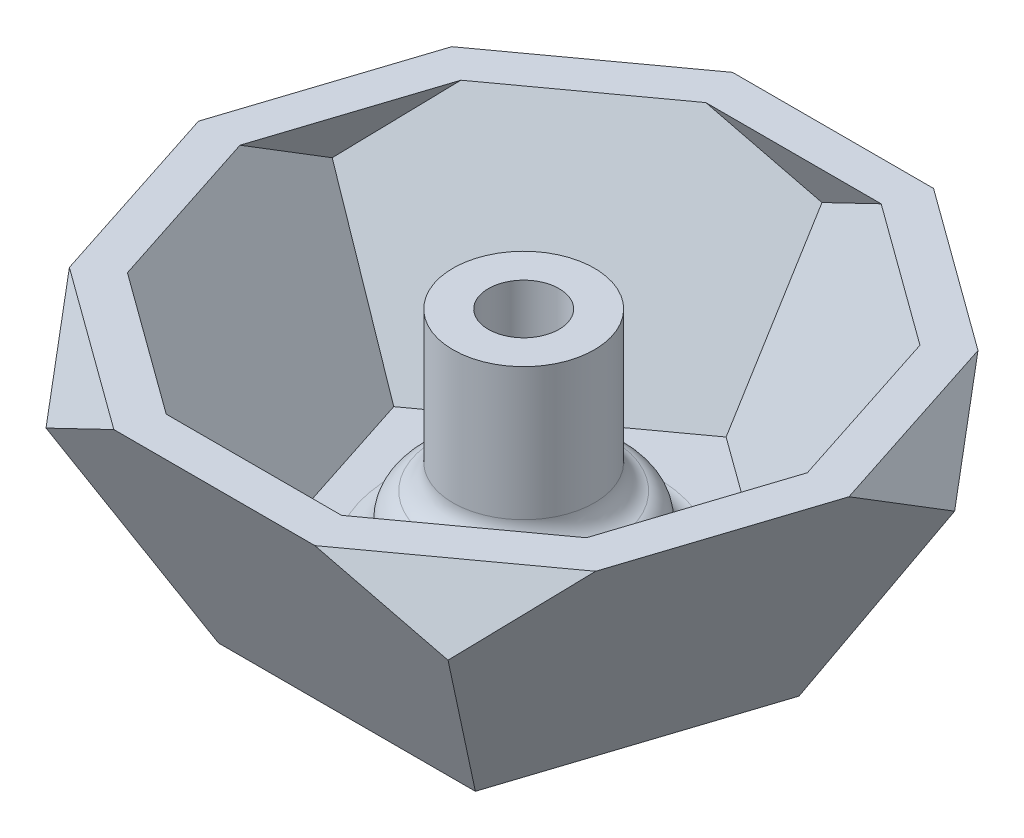
SolidWorks part; units mm, degrees
note: The reader was unsure of these and kept them because the rebuilt part matched: shared geometry of "Sketch10<3>".
ref_plane "Front Plane" through (0, 0, 0) normal (0, 0, 1) x (1, 0, 0)
ref_plane "Top Plane" through (0, 0, 0) normal (0, 1, 0) x (1, 0, 0)
ref_plane "Right Plane" through (0, 0, 0) normal (1, 0, 0) x (0, 0, -1)
sketch "Sketch1" plane through (0, 0, 0) normal (0, 1, 0) x (1, 0, 0)
  line L1 (0, 12.3607) -> (-11.7557, 3.8197)
  line L2 (-11.7557, 3.8197) -> (-7.2654, -10)
  line L3 (-7.2654, -10) -> (7.2654, -10)
  line L4 (7.2654, -10) -> (11.7557, 3.8197)
  line L5 (11.7557, 3.8197) -> (0, 12.3607)
  circle A0 centre (0, 0) radius 10 construction
  dimension "D1" = 20
extrude "Boss-Extrude1" add sketch "Sketch1" along normal blind 30 draft 26.565 draft outward yes
sketch "Sketch3" plane through (0, 30, 0) normal (0, 1, 0) x (1, 0, 0)
  line L0 (0, 0) -> (14.6946, 20.2254) construction
  line L1 (7.2654, 10) -> (-7.2654, 10)
  line L2 (-7.2654, 10) -> (-11.7557, -3.8197)
  line L3 (-11.7557, -3.8197) -> (0, -12.3607)
  line L4 (0, -12.3607) -> (11.7557, -3.8197)
  line L5 (11.7557, -3.8197) -> (7.2654, 10)
  line L6 (29.3893, 9.5492) -> (0, 30.9017) construction
  circle A0 centre (0, 0) radius 10 construction
  dimension "D1" = 20
extrude "Cut-Extrude1" cut sketch "Sketch3" against normal blind 30 draft 26.565 flip side to cut
sketch "Sketch4" plane through (0, 0, 0) normal (1, 0, 0) x (0, 0, -1)
  line L0 (-3.8197, 30) -> (-3.8197, 0) construction
  line L1 (-10, 0) -> (3.8197, 0) construction
  point P5 (-3.8197, 15)
ref_plane "Plane1" through (0, 15, 0) normal (0, 1, 0) x (1, 0, 0)
sketch "Sketch5" plane through (0, 15, 0) normal (0, 1, 0) x (1, 0, 0)
  circle A0 centre (0, 0) radius 19.3475
extrude "Cut-Extrude2" cut sketch "Sketch5" along normal blind 25
shell "Shell1" thickness 2 removed face at (0, 15, 0)
sketch "Sketch6" plane through (0, 2, 0) normal (0, 1, 0) x (1, 0, 0)
  circle A0 centre (0, 0) radius 4
  circle A1 centre (0, 0) radius 2
  dimension "D1" = 8
  dimension "D2" = 4
extrude "Boss-Extrude2" add sketch "Sketch6" along direction (0, 1, 0) on the side of the normal up to surface (13 mm away) up to face at (0, 15, 0)
ref_plane "Plane2" through (0, 3, 0) normal (0, 1, 0) x (1, 0, 0)
sketch "Sketch12" plane through (0, 3, 0) normal (0, 1, 0) x (1, 0, 0)
  line L1 (0, 11.4508) -> (-10.8904, 3.5385)
  line L2 (-10.8904, 3.5385) -> (-6.7306, -9.2639)
  line L3 (-6.7306, -9.2639) -> (6.7306, -9.2639)
  line L4 (6.7306, -9.2639) -> (10.8904, 3.5385)
  line L5 (10.8904, 3.5385) -> (0, 11.4508)
  circle A0 centre (0, 0) radius 9.2639 construction
  point P1 (0, 0)
sketch "Sketch13" plane through (0, 2, 0) normal (0, 1, 0) x (1, 0, 0)
  line L5 (10.3026, 3.3475) -> (0, 10.8328)
  line L6 (0, 10.8328) -> (-10.3026, 3.3475)
  line L7 (-10.3026, 3.3475) -> (-6.3674, -8.7639)
  line L8 (-6.3674, -8.7639) -> (6.3674, -8.7639)
  line L9 (6.3674, -8.7639) -> (10.3026, 3.3475)
  line L10 (10.3026, 3.3475) -> (0, 10.8328)
  line L11 (0, 10.8328) -> (-10.3026, 3.3475)
  line L12 (-10.3026, 3.3475) -> (-6.3674, -8.7639)
  line L13 (-6.3674, -8.7639) -> (6.3674, -8.7639)
  line L14 (6.3674, -8.7639) -> (10.3026, 3.3475)
  dimension "D1" = 0
loft "Loft1" add profiles "Sketch12", "Sketch13"
sketch "Sketch10" plane through (0, 3, 0) normal (0, 1, 0) x (1, 0, 0)
  line L1 (0, 5.1962) -> (-4.5, 2.5981)
  line L2 (-4.5, 2.5981) -> (-4.5, -2.5981)
  line L3 (-4.5, -2.5981) -> (0, -5.1962)
  line L4 (0, -5.1962) -> (4.5, -2.5981)
  line L5 (4.5, -2.5981) -> (4.5, 2.5981)
  line L6 (4.5, 2.5981) -> (0, 5.1962)
  circle A3 centre (0, 0) radius 4.5 construction
  circle A7 centre (0, 0) radius 6
  circle A8 centre (0, 0) radius 4.5 construction
  circle A9 centre (0, 0) radius 4 construction
  circle A10 centre (0, 0) radius 4
  point P5 (0, 0)
  point P13 (0, 0)
  point P15 (0, 0)
  point P16 (0, 0)
  dimension "D1" = 12
  dimension "D2" = 9
extrude "Boss-Extrude4" add sketch "Sketch10" along normal blind 3
fillet "Fillet5" radius 1.5 2 edges at (0, 6, 4) (0, 3, 6)
extrude "Cut-Extrude3" cut sketch "Sketch10<3>" against normal up to surface (3 mm away) and the other way blind 2 from offset 1 offset against normal yes
sketch "Sketch10<3>" plane through (0, 3, 0) normal (0, 1, 0) x (1, 0, 0) same geometry as "Sketch10"
fillet "Fillet6" radius 1.5 7 edges at (0, 6, 6) (4.5, 4, 0) (2.25, 4, 3.8971) (-2.25, 4, 3.8971) (-4.5, 4, 0) (-2.25, 4, -3.8971) (2.25, 4, -3.8971)
